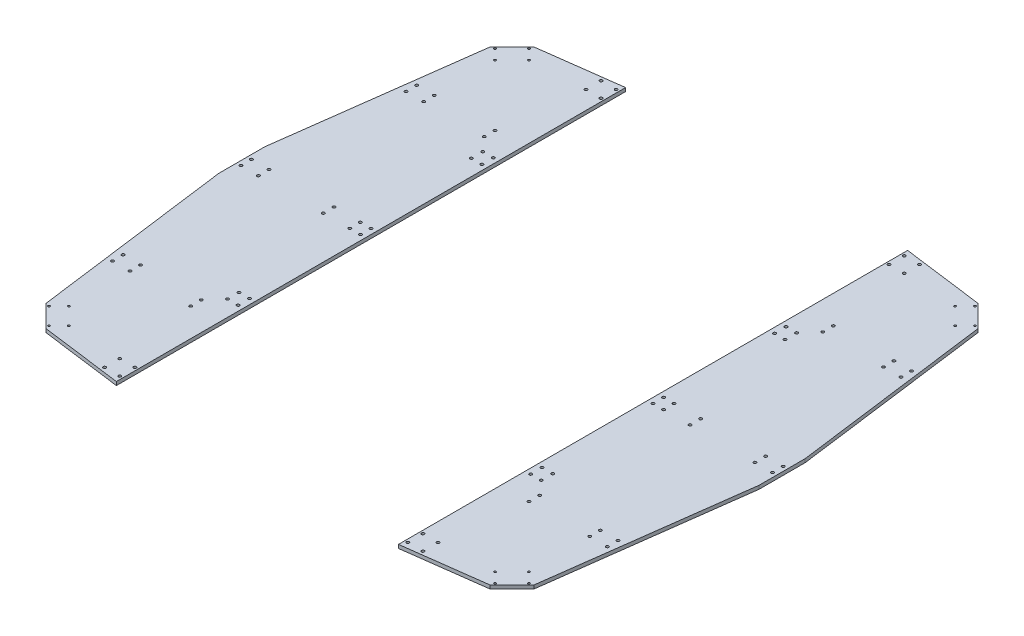
SolidWorks part; units mm, degrees
ref_plane "前视基准面" through (0, 0, 0) normal (0, 0, 1) x (1, 0, 0)
ref_plane "上视基准面" through (0, 0, 0) normal (0, 1, 0) x (1, 0, 0)
ref_plane "右视基准面" through (0, 0, 0) normal (1, 0, 0) x (0, 0, -1)
other "Configuration Table"
sketch "草图1" plane through (0, 0, 0) normal (0, 1, 0) x (1, 0, 0)
  line L0 (-314.9222, 345.9222) -> (-345.9222, 314.9222)
  line L5 (325, -325) -> (-325, 325) construction
  line L6 (325, 325) -> (-325, -325) construction
  line L7 (0, 325) -> (0, -325) construction
  line L8 (-383.07, 0) -> (383.0748, 0) construction
  line L9 (314.9222, 345.9222) -> (32.7201, 383.0748)
  line L10 (314.9222, 345.9222) -> (345.9222, 314.9222)
  line L11 (-383.07, 13.0001) -> (-230, 13.0001) construction
  line L12 (-314.9222, 345.9222) -> (-32.7201, 383.0748)
  line L13 (0, 325) -> (0, 399.6983)
  line L14 (-32.7201, 383.0748) -> (32.7201, 383.0748)
  line L15 (314.9222, -345.9222) -> (32.7201, -383.0748)
  line L16 (-32.7201, -383.0748) -> (32.7201, -383.0748)
  line L17 (-314.9222, -345.9222) -> (-32.7201, -383.0748)
  line L18 (-314.9222, -345.9222) -> (-345.9222, -314.9222)
  line L19 (-345.9222, 314.9222) -> (-383.0748, 32.7201)
  line L20 (-383.0748, -32.7201) -> (-383.0748, 32.7201)
  line L21 (-345.9222, -314.9222) -> (-383.0748, -32.7201)
  line L22 (-345.9222, -314.9222) -> (-314.9222, -345.9222)
  line L23 (345.9222, -314.9222) -> (314.9222, -345.9222)
  line L24 (345.9222, -314.9222) -> (383.0748, -32.7201)
  line L25 (383.0748, 32.7201) -> (383.0748, -32.7201)
  line L26 (345.9222, 314.9222) -> (383.0748, 32.7201)
  line L27 (-383.07, -12.9999) -> (-230, -12.9999) construction
  line L29 (361.6863, 195.182) -> (230, 195.182) construction
  line L30 (358.2633, 221.182) -> (230, 221.182) construction
  line L31 (-358.2633, 221.182) -> (-230, 221.182) construction
  line L32 (-361.6863, 195.182) -> (-230, 195.182) construction
  line L33 (361.6863, -195.182) -> (230, -195.182) construction
  line L34 (358.2633, -221.182) -> (230, -221.182) construction
  line L35 (-361.6863, -195.182) -> (-230, -195.182) construction
  line L36 (-358.2633, -221.182) -> (-230, -221.182) construction
  line L37 (-228, -357.3657) -> (-228, 357.3618) construction
  line L38 (-202, -360.7887) -> (-202, 360.7847) construction
  line L39 (383.07, 13.0001) -> (230, 13.0001) construction
  circle A5 centre (0, 0) radius 250
  circle A6 centre (302.1379, 326.1795) radius 1.5
  circle A7 centre (316.28, 340.3217) radius 1.5
  circle A8 centre (340.3217, 316.28) radius 1.5
  circle A9 centre (326.1795, 302.1379) radius 1.5
  circle A10 centre (302.1379, -326.1795) radius 1.5
  circle A11 centre (316.28, -340.3217) radius 1.5
  circle A12 centre (326.1795, -302.1379) radius 1.5
  circle A13 centre (340.3217, -316.28) radius 1.5
  circle A14 centre (-326.1795, -302.1379) radius 1.5
  circle A15 centre (-340.3217, -316.28) radius 1.5
  circle A16 centre (-302.1379, -326.1795) radius 1.5
  circle A17 centre (-316.28, -340.3217) radius 1.5
  circle A18 centre (-302.1379, 326.1795) radius 1.5
  circle A19 centre (-316.28, 340.3217) radius 1.5
  circle A20 centre (-326.1795, 302.1379) radius 1.5
  circle A21 centre (-340.3217, 316.28) radius 1.5
  circle A22 centre (350.9184, 215.682) radius 2
  circle A23 centre (377.0748, 7.5001) radius 2
  circle A24 centre (350.9184, 200.682) radius 2
  circle A25 centre (325.9184, 215.682) radius 2
  circle A26 centre (325.9184, 200.682) radius 2
  circle A27 centre (377.0748, -7.5951) radius 2
  circle A28 centre (352.0748, 7.5001) radius 2
  circle A29 centre (352.0748, -7.5951) radius 2
  circle A30 centre (350.9184, -200.682) radius 2
  circle A31 centre (350.9184, -215.682) radius 2
  circle A32 centre (325.9184, -200.682) radius 2
  circle A33 centre (325.9184, -215.682) radius 2
  circle A34 centre (-350.9184, -200.682) radius 2
  circle A35 centre (-325.9184, -200.682) radius 2
  circle A36 centre (-350.9184, -215.682) radius 2
  circle A37 centre (-325.9184, -215.682) radius 2
  circle A38 centre (-377.0748, 7.5001) radius 2
  circle A39 centre (-352.0748, 7.5001) radius 2
  circle A40 centre (-377.0748, -7.4999) radius 2
  circle A41 centre (-352.0748, -7.4999) radius 2
  circle A42 centre (-350.9184, 215.682) radius 2
  circle A43 centre (-350.9184, 200.682) radius 2
  circle A44 centre (-325.9184, 215.682) radius 2
  circle A45 centre (-325.9184, 200.682) radius 2
  circle A46 centre (-222.5, -164.8255) radius 2
  circle A47 centre (-207.5, -164.8255) radius 2
  circle A48 centre (-222.5, -181.0301) radius 2
  circle A49 centre (-207.5, -181.0301) radius 2
  circle A50 centre (-222.5, 181.0301) radius 2
  circle A51 centre (-207.5, 164.8255) radius 2
  circle A52 centre (-222.5, 164.8255) radius 2
  circle A53 centre (-207.5, 181.0301) radius 2
  circle A54 centre (207.5, -164.8255) radius 2
  circle A55 centre (222.5, -164.8255) radius 2
  circle A56 centre (207.5, -181.0301) radius 2
  circle A57 centre (222.5, -181.0301) radius 2
  circle A58 centre (207.5, 164.8255) radius 2
  circle A59 centre (222.5, 164.8255) radius 2
  circle A60 centre (207.5, 181.0301) radius 2
  circle A61 centre (222.5, 181.0301) radius 2
  circle A62 centre (-240, 215.682) radius 2
  circle A63 centre (-240, 200.682) radius 2
  circle A64 centre (-260, 7.5) radius 2
  circle A65 centre (-260, -7.5) radius 2
  circle A66 centre (-240, -200.682) radius 2
  circle A67 centre (-240, -215.682) radius 2
  circle A68 centre (240, -215.682) radius 2
  circle A69 centre (240, -200.682) radius 2
  circle A72 centre (240, 200.682) radius 2
  circle A73 centre (240, 215.682) radius 2
  circle A74 centre (207.5, 9.4052) radius 2
  circle A75 centre (222.5, 9.4052) radius 2
  circle A76 centre (207.5, -5.5948) radius 2
  circle A77 centre (222.5, -5.5948) radius 2
  circle A78 centre (-222.5, -5.5948) radius 2
  circle A79 centre (-207.5, -5.5948) radius 2
  circle A80 centre (-222.5, 9.4052) radius 2
  circle A81 centre (-207.5, 9.4052) radius 2
  circle A82 centre (260, -7.5) radius 2
  circle A83 centre (260, 7.5) radius 2
  point P0 (0, 0)
  point P13 (0, 383.0748)
  point P24 (-330.4222, -330.4222)
  point P75 (0, 0)
  point P100 (377.0748, -6.3612)
  point P103 (0, 0)
  point P178 (-254.1826, 208.328)
  point P179 (-240, 215.682)
  point P183 (-240, 200.682)
  point P187 (-260, 6.2425)
  point P188 (377.0748, -7.2605)
  point P191 (-260, -8.7575)
  point P192 (352.0865, -7.5951)
  point P195 (-240, -200.682)
  point P199 (-240, -215.682)
  point P215 (207.5, 6.2425)
  point P218 (222.5, 6.2425)
  point P219 (207.5, 6.2425)
  point P222 (207.5, -8.7575)
  point P225 (222.5, -8.7575)
  point P226 (207.5, 9.4052)
  point P227 (222.5, 9.4052)
  point P228 (207.5, -5.5948)
  point P229 (222.5, -5.5948)
  point P230 (260, 9.4052)
  point P231 (260, 9.4052)
  point P232 (260, -5.5948)
  point P241 (0, 0)
  point P244 (0, 0)
  point P245 (352.0748, 9.4052)
  point P246 (352.5845, 7.5)
  point P247 (0, 0)
  point P248 (0, 0)
  point P249 (383.0748, 0)
  point P250 (-260, -5.5948)
  point P251 (-383.07, 0.0001)
  point P252 (-260, 9.4052)
  point P253 (-260, 6.398)
  point P254 (-260, -7.2052)
  point P255 (377.0748, -5.5948)
  point P256 (0, 0)
  point P257 (377.0748, 7.5)
  point P258 (0, 0)
  point P259 (352.0748, 7.5001)
  point P261 (377.0748, 7.5001)
  dimension "D6" = 25
  dimension "D7" = 15
  dimension "D8" = 500
  dimension "D5" = 4
  dimension "D13" = 6
  dimension "D14" = 6
  dimension "D15" = 6
  dimension "D16" = 6
  dimension "D17" = 25
  dimension "D20" = 8
  dimension "D21" = 25
  dimension "D23" = 8
  dimension "D28" = 5.5
  dimension "D29" = 5.5
  dimension "D30" = 5.5
  dimension "D31" = 5.5
  dimension "D32" = 5.5
  dimension "D33" = 5.5
  dimension "D35" = 5.5
  dimension "D37" = 5.5
  dimension "D1" = 650
  dimension "D2" = 650
  dimension "D3" = 31
  dimension "D4" = 142.5
  dimension "D9" = 5.5
  dimension "D10" = 5.5
  dimension "D11" = 25
  dimension "D12" = 25
  dimension "D22" = 25
  dimension "D24" = 25
  dimension "D25" = 25
  dimension "D26" = 25
  dimension "D27" = 5.5
  dimension "D34" = 5.5
  dimension "D36" = 5.5
  dimension "D38" = 7.5001
  dimension "D39" = 7.4999
  dimension "D40" = 7.5
  dimension "D41" = 7.5
extrude "凸台-拉伸2" add sketch "草图1" along normal blind 5 contours L26 L10 L9 L14 L12 L0 L19 L20 L21 L18 L17 L16 L15 L23 L24 L25 | A13 L22 | L22 | A13 L18 region at (-172.4069, 0, -353.7562)
sketch "草图2" plane through (0, 5, 0) normal (0, 1, 0) x (1, 0, 0)
  line L0 (0, 0) -> (-330.4222, -330.4222) construction
  line L1 (0, 383.0748) -> (0, -383.0748)
  line L2 (-32.7201, 383.0748) -> (32.7201, 383.0748) construction
  line L3 (-32.7201, -383.0748) -> (32.7201, -383.0748) construction
  line L4 (-200, 361.052) -> (-200, -361.052)
  line L5 (-314.9222, 345.9222) -> (-32.7201, 383.0748) construction
  line L6 (-314.9222, -345.9222) -> (-32.7201, -383.0748) construction
  line L7 (200, 361.052) -> (200, -361.052)
  line L8 (314.9222, 345.9222) -> (32.7201, 383.0748) construction
  line L9 (314.9222, -345.9222) -> (32.7201, -383.0748) construction
  line L10 (-200, 361.052) -> (-200, 484.7149)
  line L11 (-200, 484.7149) -> (200, 484.7149)
  line L12 (200, 484.7149) -> (200, 361.052)
  line L13 (-200, -361.052) -> (-200, -418.819)
  line L14 (-200, -418.819) -> (200, -418.819)
  line L15 (200, -418.819) -> (200, -361.052)
  dimension "D1" = 200
  dimension "D2" = 200
extrude "切除-拉伸1" cut sketch "草图2" against normal blind 122 and the other way through all contours L4 L1 | L7 L1 | L7 L1 | L4 L1 | L0 L4 region at (-190.1188, 5, -422.8834)
sketch "草图3" plane through (0, 0, 0) normal (0, -1, 0) x (-1, 0, 0)
  circle A0 centre (225.7527, -352.0225) radius 2
  circle A1 centre (204.2473, -352.0225) radius 2
  circle A2 centre (225.7527, -330.517) radius 2
  circle A3 centre (204.2473, -330.517) radius 2
extrude "切除-拉伸2" cut sketch "草图3" along normal through all and the other way blind 39 contours A0 | A1 | A2 | A3
sketch "草图4" plane through (0, 5, 0) normal (0, 1, 0) x (1, 0, 0)
  line L0 (-225.7527, 352.0186) -> (-204.2473, 352.0186)
  line L1 (-215, 352.0186) -> (-215, 326.2032)
  circle A0 centre (-225.7527, 352.0186) radius 2
  circle A1 centre (-204.2473, 352.0186) radius 2
  circle A2 centre (-225.7527, 330.5131) radius 2
  circle A3 centre (-204.2473, 330.5131) radius 2
  circle A4 centre (204.2473, 330.5131) radius 2
  circle A5 centre (225.7527, 330.5131) radius 2
  circle A6 centre (204.2473, 352.0186) radius 2
  circle A7 centre (225.7527, 352.0186) radius 2
  circle A8 centre (204.2473, -352.0225) radius 2
  circle A9 centre (225.7527, -352.0225) radius 2
  circle A10 centre (204.2473, -330.517) radius 2
  circle A11 centre (225.7527, -330.517) radius 2
  dimension "D1" = 4
extrude "切除-拉伸3" cut sketch "草图4" against normal through all and the other way blind 20 contours A8 | A9 | A11 | A4 | A6 | A5 | A7 | A1 | A0 | A2 | A3 | A10 region at (-204.2473, 5, -353.962) region at (-227.6962, 5, -352.0186) region at (-225.7527, 5, -330.5131) region at (-204.2473, 5, -330.5131) region at (204.2473, 5, -330.5131) region at (225.7527, 5, -330.5131) region at (204.2473, 5, -352.0186) region at (225.7527, 5, -352.0186) region at (204.2473, 5, 352.0225) region at (225.7527, 5, 352.0225) region at (225.7527, 5, 330.517)
sketch "草图5" plane through (0, 5, 0) normal (0, 1, 0) x (1, 0, 0)
  line L0 (-200, 150) -> (-200, -150)
  line L1 (200, 150) -> (200, -150)
  line L2 (-260, 7.5) -> (-260, -7.5) construction
  line L3 (-260, -7.5) -> (-200, -7.5) construction
  line L4 (-200, -7.5) -> (-200, 7.5)
  line L5 (-200, 7.5) -> (-260, 7.5) construction
  line L6 (-228, -357.3657) -> (-228, 357.3618) construction
  line L7 (-202, -360.7887) -> (-202, 360.7847) construction
  line L8 (0, 250) -> (0, -250) construction
  line L9 (-200, 361.048) -> (-200, -361.052) construction
  circle A0 centre (0, 0) radius 250
  circle A1 centre (-222.5, 7.5) radius 2
  circle A2 centre (-207.5, 7.5) radius 2
  circle A3 centre (-222.5, -7.5) radius 2
  circle A4 centre (-207.5, -7.5) radius 2
  circle A5 centre (207.5, -7.5) radius 2
  circle A6 centre (222.5, -7.5) radius 2
  circle A7 centre (207.5, 7.5) radius 2
  circle A8 centre (222.5, 7.5) radius 2
  point P39 (-200, 8.9217)
  point P42 (0, 0)
  point P43 (-207.5, 9.4052)
  point P44 (207.5, -5.5948)
  point P45 (222.5, 9.4052)
  point P46 (-207.5, -7.5)
  dimension "D1" = 5.5
  dimension "D2" = 5.5
  dimension "D3" = 5.5
  dimension "D4" = 5.5
extrude "凸台-拉伸3" add sketch "草图5" against normal blind 5 contours L0 | L1 A0 region at (-220.2076, 5, 0) region at (220.2076, 5, 0)
